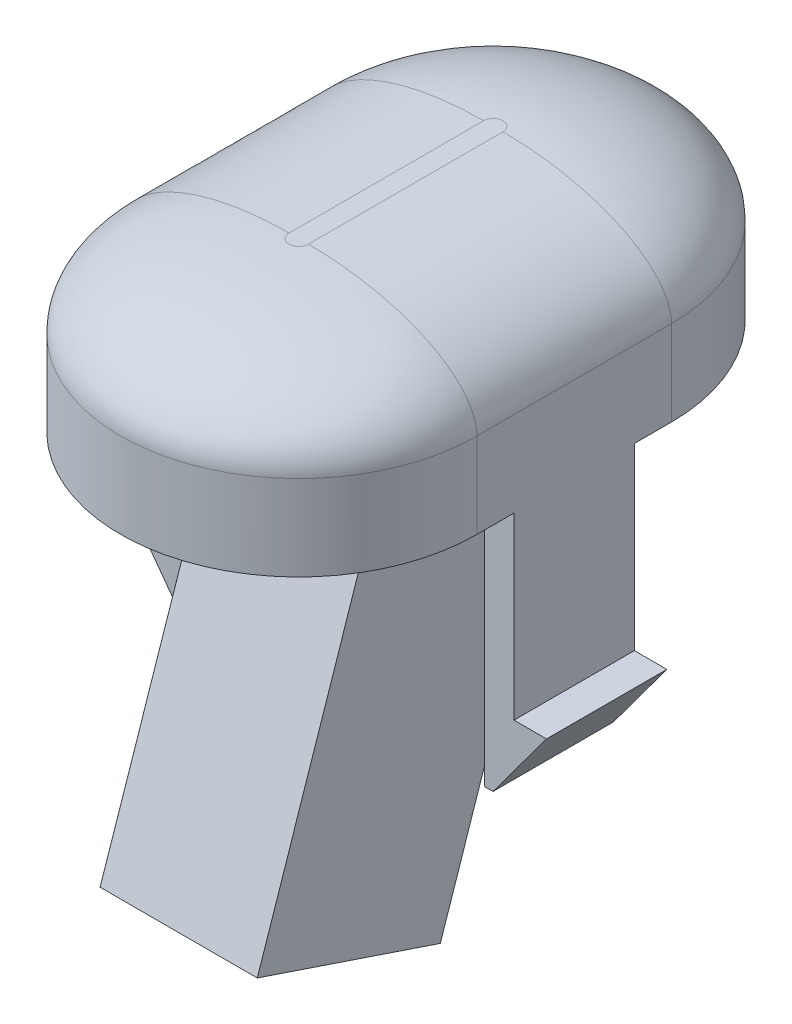
SolidWorks part; units mm, degrees
ref_plane "Front Plane" through (0, 0, 0) normal (0, 0, 1) x (1, 0, 0)
ref_plane "Top Plane" through (0, 0, 0) normal (0, 1, 0) x (1, 0, 0)
ref_plane "Right Plane" through (0, 0, 0) normal (1, 0, 0) x (0, 0, -1)
sketch "Sketch1" plane through (0, 0, 0) normal (0, 1, 0) x (1, 0, 0)
  line L1 (0, 0) -> (14.8, 0)
  line L2 (0, 0) -> (0, -8.08)
  line L3 (0, -8.08) -> (14.8, -8.08)
  line L4 (14.8, 0) -> (14.8, -8.08)
  arc A0 (0, 0) -> (14.8, 0) centre (7.4, 0) cw
  arc A1 (0, -8.08) -> (14.8, -8.08) centre (7.4, -8.08) ccw
  dimension "D2" = 8.08
  dimension "D1" = 14.8
extrude "Boss-Extrude1" add sketch "Sketch1" along normal blind 6.94 contours L3 A1 | L4 L1 L2 L3 | A0 L1 region at (7.4, 0, -3.1407) region at (7.4, 0, 4.04) region at (7.4, 0, 11.2207)
fillet "Fillet1" radius 7 4 edges at (7.4, 6.94, -7.4) (0, 6.94, 4.04) (7.4, 6.94, 15.48) (14.8, 6.94, 4.04) second distance 3.4 first distance on face at (7.4, 6.94, 4.04)
sketch "Sketch2" plane through (0, 0, 0) normal (0, -1, 0) x (1, 0, 0)
  line L0 (0, 0) -> (0, 8.08) construction
  line L1 (0, 6.54) -> (2.5, 6.54)
  line L2 (0, 6.54) -> (0, 1.54)
  line L3 (0, 1.54) -> (2.5, 1.54)
  line L4 (2.5, 6.54) -> (2.5, 1.54)
  line L5 (14.8, 0) -> (14.8, 8.08) construction
  line L6 (14.8, 6.54) -> (12.3, 6.54)
  line L7 (14.8, 6.54) -> (14.8, 1.54)
  line L8 (14.8, 1.54) -> (12.3, 1.54)
  line L9 (12.3, 6.54) -> (12.3, 1.54)
  dimension "D1" = 2.5
  dimension "D2" = 5
  dimension "D3" = 1.54
extrude "Boss-Extrude2" add sketch "Sketch2" along normal blind 7.45
sketch "Sketch3" plane through (0, -7.45, 0) normal (0, -1, 0) x (-1, 0, 0)
  line L0 (-14.8, -6.54) -> (-12.3, -6.54) construction
  line L1 (-2.5, -1.54) -> (1.94, -1.54)
  line L2 (-2.5, -1.54) -> (-2.5, -6.54)
  line L3 (-2.5, -6.54) -> (1.94, -6.54)
  line L4 (1.94, -1.54) -> (1.94, -6.54)
  line L5 (-12.3, -6.54) -> (-16.74, -6.54)
  line L6 (-12.3, -6.54) -> (-12.3, -1.54)
  line L7 (-12.3, -1.54) -> (-16.74, -1.54)
  line L8 (-16.74, -6.54) -> (-16.74, -1.54)
  line L9 (-12.3, -6.54) -> (-12.3, -1.54) construction
  line L10 (0, -6.54) -> (0, -1.54) construction
  dimension "D1" = 1.94
extrude "Boss-Extrude3" add sketch "Sketch3" along normal blind 3
sketch "Sketch4" plane through (0, 0, 1.54) normal (0, 0, -1) x (-1, 0, 0)
  line L0 (1.94, -7.45) -> (-0.28, -10.45)
  line L2 (-0.28, -10.45) -> (1.94, -10.45)
  line L3 (1.94, -10.45) -> (1.94, -7.45)
  line L4 (-16.74, -7.45) -> (-16.74, -10.45)
  line L5 (-16.74, -10.45) -> (-14.52, -10.45)
  line L6 (-12.3, -10.45) -> (-16.74, -10.45) construction
  line L7 (-14.52, -10.45) -> (-16.74, -7.45)
  line L9 (1.94, -10.45) -> (-2.5, -10.45) construction
extrude "Cut-Extrude1" cut sketch "Sketch4" against normal up to next
sketch "Sketch5" plane through (0, 0, 1.54) normal (0, 0, -1) x (-1, 0, 0)
  line L0 (-0.28, -10.45) -> (-0.87, -10.45)
  line L1 (-0.28, -10.45) -> (-2.5, -10.45) construction
  line L2 (-0.87, -10.45) -> (1.35, -7.45)
  line L3 (1.94, -7.45) -> (0, -7.45) construction
  line L4 (1.35, -7.45) -> (1.94, -7.45)
  line L5 (1.94, -7.45) -> (-0.28, -10.45)
  line L6 (-14.52, -10.45) -> (-13.93, -10.45)
  line L7 (-12.3, -10.45) -> (-14.52, -10.45) construction
  line L8 (-13.93, -10.45) -> (-16.15, -7.45)
  line L9 (-14.8, -7.45) -> (-16.74, -7.45) construction
  line L10 (-16.15, -7.45) -> (-16.74, -7.45)
  line L11 (-16.74, -7.45) -> (-14.52, -10.45)
  dimension "D1" = 1.35
extrude "Cut-Extrude2" cut sketch "Sketch5" against normal up to next
sketch "Sketch6" plane through (0, 0, 1.54) normal (0, 0, -1) x (-1, 0, 0)
  line L0 (0, 0) -> (-2.5, 0) construction
  line L1 (-2.5, -10.45) -> (-1.23, -10.45)
  line L2 (-2.5, -10.45) -> (-2.5, 0)
  line L3 (-2.5, 0) -> (-1.23, 0)
  line L4 (-1.23, -10.45) -> (-1.23, 0)
  line L5 (-12.3, 0) -> (-14.8, 0) construction
  line L6 (-12.3, -10.45) -> (-13.57, -10.45)
  line L7 (-12.3, -10.45) -> (-12.3, 0)
  line L8 (-12.3, 0) -> (-13.57, 0)
  line L9 (-13.57, -10.45) -> (-13.57, 0)
  dimension "D1" = 1.27
extrude "Cut-Extrude3" cut sketch "Sketch6" against normal up to next
sketch "Sketch7" plane through (0, 0, 0) normal (0, -1, 0) x (1, 0, 0)
  line L0 (1.23, 6.54) -> (1.23, 1.54) construction
  line L1 (4.135, 6.54) -> (10.6628, 6.54)
  line L2 (4.135, 6.54) -> (4.135, 1.54)
  line L3 (4.135, 1.54) -> (10.6628, 1.54)
  line L4 (10.6628, 6.54) -> (10.6628, 1.54)
  line L6 (1.23, 6.54) -> (0, 6.54) construction
  line L8 (0, 1.54) -> (1.23, 1.54) construction
  line L10 (4.135, 6.54) -> (10.6628, 6.54)
  line L11 (4.135, 6.54) -> (4.135, 7.84)
  line L12 (4.135, 7.84) -> (10.6628, 7.84)
  line L13 (10.6628, 6.54) -> (10.6628, 7.84)
  line L14 (4.135, 1.54) -> (10.6628, 1.54)
  line L15 (4.135, 1.54) -> (4.135, 0.24)
  line L16 (4.135, 0.24) -> (10.6628, 0.24)
  line L17 (10.6628, 1.54) -> (10.6628, 0.24)
  dimension "D1" = 6.5278
  dimension "D2" = 2.905
  dimension "D3" = 1.3
extrude "Boss-Extrude4" add sketch "Sketch7" along normal blind 2.5563 contours L4 L1 L2 L3 | L17 L3 L15 L16 | L1 L13 L12 L11 region at (7.3989, 0, 7.19) region at (7.3989, 0, 4.04) region at (7.3989, 0, 0.89)
sketch "Sketch8" plane through (10.6628, 0, 0) normal (1, 0, 0) x (0, 0, -1)
  line L0 (-0.24, -2.5563) -> (-7.84, 0)
  line L1 (-7.84, 0) -> (-7.84, -2.5563)
  line L2 (-7.84, -2.5563) -> (-7.84, 0) construction
  line L3 (-7.84, -2.5563) -> (-0.24, -2.5563)
extrude "Cut-Extrude4" cut sketch "Sketch8" against normal up to next
sketch "Sketch9" plane through (0, -2.369, 0.7969) normal (0, -0.9478, 0.3188) x (1, 0, 0)
  line L0 (10.6628, -0.5875) -> (10.6628, 7.4309) construction
  line L1 (4.135, -0.5875) -> (10.6628, -0.5875)
  line L2 (4.135, -0.5875) -> (4.135, 0.4828)
  line L3 (4.135, 0.4828) -> (10.6628, 0.4828)
  line L4 (10.6628, -0.5875) -> (10.6628, 0.4828)
  line L5 (4.135, 7.4309) -> (4.135, -0.5875) construction
  line L6 (9.5631, 0.4828) -> (10.6628, 0.4828)
  line L7 (9.5631, 0.4828) -> (9.5631, 6.3605)
  line L8 (9.5631, 6.3605) -> (10.6628, 6.3605)
  line L9 (10.6628, 0.4828) -> (10.6628, 6.3605)
  line L10 (5.2348, 0.4828) -> (4.135, 0.4828)
  line L11 (5.2348, 0.4828) -> (5.2348, 6.3605)
  line L12 (5.2348, 6.3605) -> (4.135, 6.3605)
  line L13 (4.135, 0.4828) -> (4.135, 6.3605)
  line L15 (4.135, 6.3605) -> (10.6628, 6.3605)
  line L16 (4.135, 6.3605) -> (4.135, 7.4309)
  line L17 (4.135, 7.4309) -> (10.6628, 7.4309)
  line L18 (10.6628, 6.3605) -> (10.6628, 7.4309)
  dimension "D1" = 5.8777
  dimension "D2" = 4.3283
extrude "Boss-Extrude5" add sketch "Sketch9" along normal blind 16.3863 contours L3 L7 L0 L1 | L11 L12 L7 L3 | L8 L7 L3 L1 | L12 L15 L8 L1 L3 L7 region at (7.3989, -2.3857, 0.7473) region at (10.1129, -1.2782, 4.04) region at (7.3989, -0.1706, 7.3327) region at (4.6849, -1.2782, 4.04)
